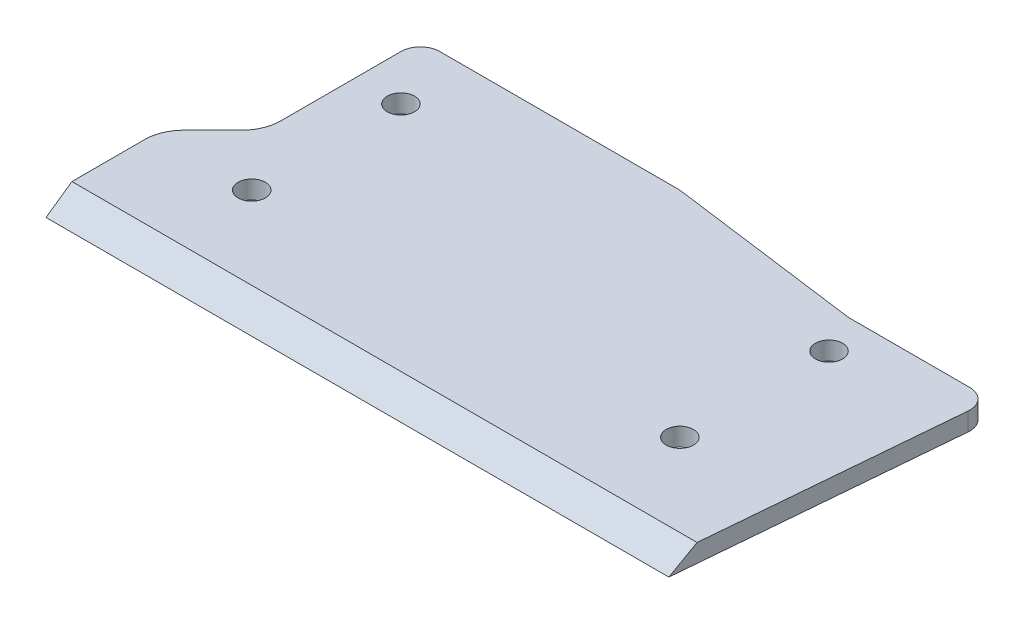
SolidWorks part; units mm, degrees
material "Titanium Ti-8Al-1Mo-1V"
ref_plane "Front Plane" through (0, 0, 0) normal (0, 0, 1) x (1, 0, 0)
ref_plane "Top Plane" through (0, 0, 0) normal (0, 1, 0) x (1, 0, 0)
ref_plane "Right Plane" through (0, 0, 0) normal (1, 0, 0) x (0, 0, -1)
sketch "Sketch1" plane through (0, 0, 0) normal (0, 1, 0) x (1, 0, 0)
  line L1 (0, 4) -> (40, 4)
  line L2 (40, 4) -> (70, 0)
  line L3 (70, 0) -> (92, 0)
  line L4 (92, 0) -> (88, -46)
  line L5 (88, -46) -> (0, -46)
  line L7 (0, -46) -> (-8, -46)
  line L8 (-8, -46) -> (-8, -28)
  line L9 (-8, -28) -> (0, -20)
  line L11 (0, 4) -> (0, -20)
  dimension "D1" = 46
  dimension "D2" = 22
  dimension "D3" = 30
  dimension "D4" = 88
  dimension "D5" = 40
  dimension "D6" = 4
  dimension "D7" = 8
  dimension "D8" = 18
  dimension "D9" = 8
extrude "Boss-Extrude1" add sketch "Sketch1" along normal blind 2.8
sketch "Sketch2" plane through (0, 2.8, 0) normal (0, 1, 0) x (1, 0, 0)
  line L1 (92, 0) -> (70, 0) construction
  line L2 (0, 4) -> (0, -20) construction
  circle A0 centre (7, -6) radius 2.1
  circle A1 centre (7, -29) radius 2.1
  circle A2 centre (73, -6) radius 2.1
  circle A3 centre (73, -29) radius 2.1
  dimension "D2" = 4.2
  dimension "D5" = 4.2
  dimension "D1" = 7
  dimension "D3" = 6
  dimension "D4" = 23
  dimension "D7" = 66
  dimension "D6" = 2
extrude "Cut-Extrude1" cut sketch "Sketch2" against normal through all
fillet "Fillet1" radius 6 2 edges at (0, 1.4, 20) (-8, 1.4, 28)
chamfer "Chamfer1" [suppressed] distance 2 angle 45
chamfer "Chamfer2" distance 3 angle 55 1 edges at (40, 2.8, 46) first distance on face at (40, 1.4, 46)
fillet "Fillet2" radius 3 2 edges at (0, 1.4, -4) (92, 1.4, 0)
